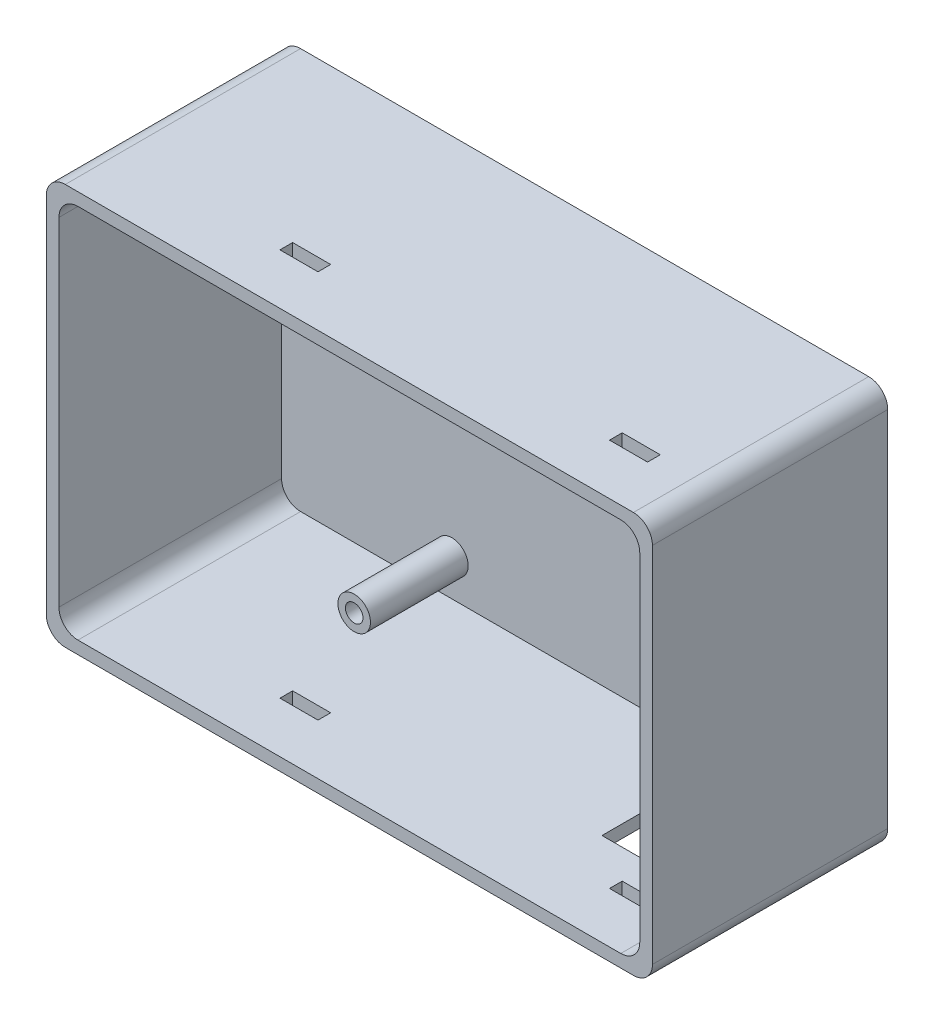
SolidWorks part; units mm, degrees
note: The reader was unsure of these and kept them because the rebuilt part matched: shared geometry of "Sketch2<12>", "Sketch4<6>", "Sketch2<14>", "Sketch2<16>".
ref_plane "Front Plane" through (0, 0, 0) normal (0, 0, 1) x (1, 0, 0)
ref_plane "Top Plane" through (0, 0, 0) normal (0, 1, 0) x (1, 0, 0)
ref_plane "Right Plane" through (0, 0, 0) normal (1, 0, 0) x (0, 0, -1)
sketch "Sketch2" plane through (0, 0, 0) normal (0, 0, 1) x (1, 0, 0)
  line L0 (101.583, -66.6) -> (193.2196, -66.6) construction
  line L1 (193.2196, -66.6) -> (193.2196, -125.8557) construction
  line L2 (193.2196, -125.8557) -> (101.583, -125.8557) construction
  line L3 (101.583, -125.8557) -> (101.583, -66.6) construction
  line L5 (186.4527, -64.6) -> (180.4527, -64.6)
  line L6 (186.4527, -64.6) -> (186.4527, -66.6)
  line L7 (186.4527, -66.6) -> (180.4527, -66.6)
  line L8 (180.4527, -64.6) -> (180.4527, -66.6)
  line L9 (102.583, -121.1707) -> (102.583, -105.2907) construction
  line L10 (117.8921, -99.3741) -> (109.6079, -99.3741)
  line L11 (117.8921, -99.3741) -> (117.8921, -107.0259)
  line L12 (117.8921, -107.0259) -> (109.6079, -107.0259)
  line L13 (109.6079, -99.3741) -> (109.6079, -107.0259)
  line L14 (113.75, -107.0259) -> (113.75, -99.3741) construction
  line L15 (117.8921, -103.2) -> (109.6079, -103.2) construction
  line L16 (117.7591, -118.815) -> (109.6079, -118.815)
  line L17 (117.7591, -118.815) -> (117.7591, -110.911)
  line L18 (117.7591, -110.911) -> (109.6079, -110.911)
  line L19 (109.6079, -118.815) -> (109.6079, -110.911)
  line L20 (113.6835, -110.911) -> (113.6835, -118.815) construction
  line L21 (117.7591, -114.863) -> (109.6079, -114.863) construction
  line L26 (101.583, -66.6) -> (193.2196, -125.8557) construction
  line L27 (101.583, -125.8557) -> (193.2196, -66.6) construction
  line L28 (186.2412, -113.29) -> (188.4605, -113.29)
  line L29 (186.2412, -113.29) -> (186.2412, -115.4412)
  line L30 (186.2412, -115.4412) -> (188.4605, -115.4412)
  line L31 (188.4605, -113.29) -> (188.4605, -115.4412)
  line L32 (187.3509, -115.4412) -> (187.3509, -113.29) construction
  line L33 (186.2412, -114.3656) -> (188.4605, -114.3656) construction
  line L34 (188.4605, -113.29) -> (127.7403, -113.29)
  line L35 (188.4605, -113.29) -> (188.4605, -115.4412)
  line L36 (188.4605, -115.4412) -> (127.7403, -115.4412)
  line L37 (127.7403, -113.29) -> (127.7403, -115.4412)
  line L38 (188.4605, -113.29) -> (127.7403, -115.4412) construction
  line L39 (188.4605, -115.4412) -> (127.7403, -113.29) construction
  line L40 (127.7403, -96.8367) -> (188.4605, -96.8367)
  line L41 (127.7403, -96.8367) -> (127.7403, -99.0011)
  line L42 (127.7403, -99.0011) -> (188.4605, -99.0011)
  line L43 (188.4605, -96.8367) -> (188.4605, -99.0011)
  line L44 (127.7403, -96.8367) -> (188.4605, -99.0011) construction
  line L45 (127.7403, -99.0011) -> (188.4605, -96.8367) construction
  line L46 (171.1724, -93.2559) -> (177.2539, -93.2559)
  line L47 (171.1724, -93.2559) -> (171.1724, -76.924)
  line L48 (171.1724, -76.924) -> (177.2539, -76.924)
  line L49 (177.2539, -93.2559) -> (177.2539, -76.924)
  line L50 (171.1724, -93.2559) -> (177.2539, -76.924) construction
  line L51 (171.1724, -76.924) -> (177.2539, -93.2559) construction
  line L52 (154.5686, -80.919) -> (156.5909, -80.919)
  line L53 (154.5686, -80.919) -> (154.5686, -93.2559)
  line L54 (154.5686, -93.2559) -> (156.5909, -93.2559)
  line L55 (156.5909, -80.919) -> (156.5909, -93.2559)
  line L56 (154.5686, -80.919) -> (156.5909, -93.2559) construction
  line L57 (154.5686, -93.2559) -> (156.5909, -80.919) construction
  line L58 (125.2342, -95.0818) -> (101.583, -95.0818)
  line L59 (125.2342, -95.0818) -> (125.2342, -66.6)
  line L60 (125.2342, -66.6) -> (101.583, -66.6)
  line L61 (101.583, -95.0818) -> (101.583, -66.6)
  line L62 (125.2342, -95.0818) -> (101.583, -66.6) construction
  line L63 (125.2342, -66.6) -> (101.583, -95.0818) construction
  line L64 (181.8141, -93.2559) -> (188.4605, -93.2559)
  line L65 (181.8141, -93.2559) -> (181.8141, -77.8601)
  line L66 (181.8141, -77.8601) -> (188.4605, -77.8601)
  line L67 (188.4605, -93.2559) -> (188.4605, -77.8601)
  line L68 (181.8141, -93.2559) -> (188.4605, -77.8601) construction
  line L69 (181.8141, -77.8601) -> (188.4605, -93.2559) construction
  line L70 (101.583, -66.6) -> (193.2196, -66.6)
  line L71 (101.583, -66.6) -> (101.583, -125.8557)
  line L72 (101.583, -125.8557) -> (193.2196, -125.8557)
  line L73 (193.2196, -66.6) -> (193.2196, -125.8557)
  line L74 (101.583, -66.6) -> (193.2196, -125.8557) construction
  line L75 (101.583, -125.8557) -> (193.2196, -66.6) construction
  line L76 (99.583, -64.6) -> (195.2196, -64.6)
  line L77 (99.583, -64.6) -> (99.583, -127.8557)
  line L78 (99.583, -127.8557) -> (195.2196, -127.8557)
  line L79 (195.2196, -64.6) -> (195.2196, -127.8557)
  line L80 (99.583, -64.6) -> (195.2196, -127.8557) construction
  line L81 (99.583, -127.8557) -> (195.2196, -64.6) construction
  line L82 (186.4527, -64.6) -> (180.4527, -66.6) construction
  line L83 (186.4527, -66.6) -> (180.4527, -64.6) construction
  line L84 (153.2237, -124.8557) -> (157.563, -124.8557) construction
  line L85 (128.455, -66.6) -> (134.455, -66.6)
  line L86 (192.2196, -100.2507) -> (192.2196, -90.2507) construction
  line L87 (108, -67.6) -> (187, -67.6) construction
  line L88 (128.455, -66.6) -> (128.455, -64.6)
  line L89 (128.455, -64.6) -> (134.455, -64.6)
  line L90 (134.455, -66.6) -> (134.455, -64.6)
  line L91 (128.455, -66.6) -> (134.455, -64.6) construction
  line L92 (128.455, -64.6) -> (134.455, -66.6) construction
  line L93 (186.4527, -125.8557) -> (180.4527, -125.8557)
  line L94 (186.4527, -125.8557) -> (186.4527, -127.8557)
  line L95 (186.4527, -127.8557) -> (180.4527, -127.8557)
  line L96 (180.4527, -125.8557) -> (180.4527, -127.8557)
  line L97 (186.4527, -125.8557) -> (180.4527, -127.8557) construction
  line L98 (186.4527, -127.8557) -> (180.4527, -125.8557) construction
  line L99 (128.4907, -125.8557) -> (134.4907, -125.8557)
  line L100 (128.4907, -125.8557) -> (128.4907, -127.8557)
  line L101 (128.4907, -127.8557) -> (134.4907, -127.8557)
  line L102 (134.4907, -125.8557) -> (134.4907, -127.8557)
  line L103 (128.4907, -125.8557) -> (134.4907, -127.8557) construction
  line L104 (128.4907, -127.8557) -> (134.4907, -125.8557) construction
  circle A0 centre (129.3868, -70.0619) radius 0.0023
  circle A1 centre (128.455, -71.07) radius 1.375
  circle A2 centre (186.4527, -120.0603) radius 1.3886
  circle A3 centre (128.455, -120.0603) radius 1.3847
  circle A4 centre (186.4527, -71.07) radius 1.3727
  circle A5 centre (128.455, -71.07) radius 2.5785
  circle A6 centre (186.4527, -71.07) radius 2.5588
  circle A7 centre (128.455, -120.0603) radius 2.5686
  circle A8 centre (186.4527, -120.0603) radius 2.5684
  circle A9 centre (128.455, -71.07) radius 1.375
  point P2 (147.4013, -96.2279)
  point P8 (147.4013, -96.2279)
  point P11 (102.583, -113.2307)
  point P14 (113.75, -103.2)
  point P18 (113.6835, -114.863)
  point P23 (187.3509, -114.3656)
  point P24 (147.4013, -96.2279)
  point P30 (158.1004, -114.3656)
  point P35 (158.1004, -97.9189)
  point P40 (174.2131, -85.09)
  point P45 (155.5797, -87.0875)
  point P50 (113.4086, -80.8409)
  point P54 (185.1373, -85.558)
  point P73 (183.4527, -65.6)
  point P78 (131.455, -65.6)
  point P83 (183.4527, -126.8557)
  point P88 (131.4907, -126.8557)
  dimension "D1" = 2
  dimension "D2" = 2
  dimension "D3" = 2
  dimension "D4" = 2
  dimension "D5" = 1
  dimension "D6" = 1
  dimension "D7" = 1
  dimension "D8" = 1
  dimension "D9" = 6
  dimension "D10" = 6
  dimension "D11" = 6
  dimension "D12" = 6
extrude "Perimeter" add sketch "Sketch2" against normal blind 31 and the other way up to surface (4.1245 mm away) contours L79 L76 L77 L78 L70 L73 L72 L71 L61 L60
sketch "Sketch4" plane through (0, 0, 0) normal (0, 1, 0) x (1, 0, 0)
  line L0 (179.2257, 14.5885) -> (179.5957, 14.5885) construction
  line L1 (172.6248, 10.512) -> (186.1966, 10.512)
  line L2 (172.6248, 10.512) -> (172.6248, 18.6649)
  line L3 (172.6248, 18.6649) -> (186.1966, 18.6649)
  line L4 (186.1966, 10.512) -> (186.1966, 18.6649)
  line L5 (179.4107, 18.6649) -> (179.4107, 10.512) construction
  line L6 (172.6248, 14.5885) -> (186.1966, 14.5885) construction
  line L7 (184.9716, 18.6649) -> (187.4216, 18.6649) construction
  line L8 (99.583, -6.1245) -> (99.583, -4.1245) construction
  line L9 (194.2196, -0.0726) -> (99.583, -0.0726)
  line L10 (194.2196, -0.0726) -> (194.2196, 29.7749)
  line L11 (194.2196, 29.7749) -> (99.583, 29.7749)
  line L12 (99.583, -0.0726) -> (99.583, 29.7749)
  line L13 (194.2196, -0.0726) -> (99.583, 29.7749) construction
  line L14 (194.2196, 29.7749) -> (99.583, -0.0726) construction
  line L15 (119.5007, 28.7749) -> (103.6207, 28.7749) construction
  line L16 (128.455, 5.8755) -> (134.455, 5.8755) construction
  line L17 (194.2196, 29.7749) -> (99.583, 29.7749)
  line L18 (194.2196, 29.7749) -> (194.2196, 35.4274)
  line L19 (194.2196, 35.4274) -> (99.583, 35.4274)
  line L20 (99.583, 29.7749) -> (99.583, 35.4274)
  line L21 (194.2196, 29.7749) -> (99.583, 35.4274) construction
  line L22 (194.2196, 35.4274) -> (99.583, 29.7749) construction
  line L23 (186.4527, 5.8755) -> (180.4527, 5.8755)
  line L24 (186.4527, 5.8755) -> (186.4527, 3.8732)
  line L25 (186.4527, 3.8732) -> (180.4527, 3.8732)
  line L26 (180.4527, 5.8755) -> (180.4527, 3.8732)
  line L27 (186.4527, 5.8755) -> (180.4527, 3.8732) construction
  line L28 (186.4527, 3.8732) -> (180.4527, 5.8755) construction
  line L29 (186.4527, 5.8755) -> (180.4527, 5.8755) construction
  line L30 (134.455, 5.8755) -> (128.455, 5.8755)
  line L31 (134.455, 5.8755) -> (134.455, 3.8732)
  line L32 (134.455, 3.8732) -> (128.455, 3.8732)
  line L33 (128.455, 5.8755) -> (128.455, 3.8732)
  line L34 (134.455, 5.8755) -> (128.455, 3.8732) construction
  line L35 (134.455, 3.8732) -> (128.455, 5.8755) construction
  point P0 (179.4107, 14.5885)
  point P12 (146.9013, 14.8511)
  point P15 (99.583, -5.1245)
  point P20 (146.9013, 32.6011)
  point P25 (183.4527, 4.8744)
  point P32 (131.455, 4.8744)
  dimension "D1" = 0
  dimension "D2" = 1
  dimension "D3" = 35.5
  dimension "D4" = 0
  dimension "D5" = 0
extrude "USB_Hole" cut sketch "Sketch4" against normal blind 81 from surface at -66.6 contours L1 L4 L3 L2 starting at face at (147.4013, -66.6, -13.4378)
extrude "Bottom" add sketch "Sketch2<12>" against normal blind 2 from surface at -31 contours L76 L79 L78 L77 starting at face at (147.4013, -96.2279, -31)
sketch "Sketch2<12>" plane through (0, 0, 0) normal (0, 0, 1) x (1, 0, 0) same geometry as "Sketch2"
extrude "Locking_Hole" cut sketch "Sketch4<6>" against normal blind 152 contours L30 L33 L32 L31 | L23 L26 L25 L24
sketch "Sketch4<6>" plane through (0, 0, 0) normal (0, 1, 0) x (1, 0, 0) same geometry as "Sketch4"
fillet "Fillet1" radius 3 8 edges at (101.583, -125.8557, -13.4378) (99.583, -127.8557, -14.4378) (195.2196, -127.8557, -14.4378) (193.2196, -125.8557, -13.4378) (193.2196, -66.6, -13.4378) (195.2196, -64.6, -14.4378) (101.583, -66.6, -13.4378) (99.583, -64.6, -14.4378)
extrude "Straws" add sketch "Sketch2<14>" along normal up to surface (15.4151 mm away) from surface at -31 contours A5 A1 | A6 A4 | A7 A3 | A8 A2 | L71 L70 L73 L72
sketch "Sketch2<14>" plane through (0, 0, 0) normal (0, 0, 1) x (1, 0, 0) same geometry as "Sketch2"
extrude "Cut-Extrude3" cut sketch "Sketch2<16>" against normal blind 68 contours A1 | A4 | A3 | A2
sketch "Sketch2<16>" plane through (0, 0, 0) normal (0, 0, 1) x (1, 0, 0) same geometry as "Sketch2"
